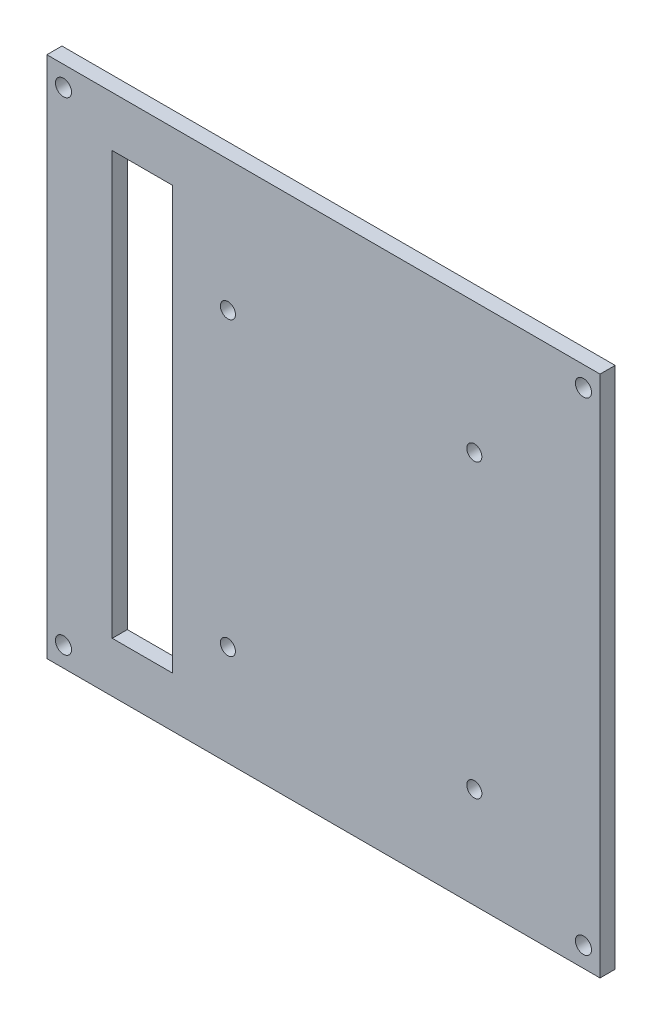
SolidWorks part; units mm, degrees
ref_plane "Alzado" through (0, 0, 0) normal (0, 0, 1) x (1, 0, 0)
ref_plane "Planta" through (0, 0, 0) normal (0, 1, 0) x (1, 0, 0)
ref_plane "Vista lateral" through (0, 0, 0) normal (1, 0, 0) x (0, 0, -1)
sketch "Croquis1" plane through (0, 0, 0) normal (0, 0, 1) x (1, 0, 0)
  line L1 (0, 82) -> (110, 82)
  line L2 (0, 82) -> (0, -10)
  line L3 (0, -10) -> (110, -10)
  line L4 (110, 82) -> (110, -10)
  line L5 (0, 82) -> (110, 82)
  line L9 (0, -10) -> (110, -10)
  dimension "D1" = 110
  dimension "D2" = 92
extrude "Saliente-Extruir1" add sketch "Croquis1" along normal blind 3 contours L1 | L3 | L2 L3 L4 L1 region at (55, 36, 0)
sketch "Croquis7" plane through (0, 82, 0) normal (0, 1, 0) x (1, 0, 0)
  line L1 (0, 0) -> (110, 0)
  line L2 (0, 0) -> (0, -3)
  line L3 (0, -3) -> (110, -3)
  line L4 (110, 0) -> (110, -3)
extrude "Saliente-Extruir2" add sketch "Croquis7" along normal blind 6
sketch "Croquis8" plane through (0, -10, 0) normal (0, -1, 0) x (1, 0, 0)
  line L1 (0, 3) -> (110, 3)
  line L2 (0, 3) -> (0, 0)
  line L3 (0, 0) -> (110, 0)
  line L4 (110, 3) -> (110, 0)
extrude "Saliente-Extruir3" add sketch "Croquis8" along normal blind 6
sketch "Croquis9" plane through (0, 0, 3) normal (0, 0, 1) x (1, 0, 0)
  line L1 (110, 88) -> (110, -16) construction
  line L3 (110, -16) -> (0, -16) construction
  circle A0 centre (97.5, -6) radius 2.5
  dimension "D1" = 5
  dimension "D3" = 10
  dimension "D2" = 12.5
sketch "Croquis11" plane through (0, 0, 3) normal (0, 0, 1) x (1, 0, 0)
  line L0 (0, 84) -> (110, 84) construction
  line L1 (0, 88) -> (0, -16) construction
  line L2 (110, 88) -> (110, -16) construction
  line L3 (3.3, 88) -> (3.3, -16) construction
  line L4 (0, 88) -> (110, 88) construction
  line L5 (110, -16) -> (0, -16) construction
  line L6 (106.7, 88) -> (106.7, -16) construction
  line L7 (0, -12) -> (110, -12) construction
  dimension "D1" = 4
  dimension "D2" = 3.3
  dimension "D3" = 3.3
  dimension "D4" = 4
hole_wizard "Taladro de margen para M31" positions "Croquis3D2" profile "Croquis12" hole size "M3" standard "ISO" end condition through all
sketch3d "Croquis3D2"
  line L0 (0, 84, 3) -> (110, 84, 3) construction
  line L1 (3.3, 88, 3) -> (3.3, -16, 3) construction
  line L2 (0, -12, 3) -> (110, -12, 3) construction
  line L3 (106.7, 88, 3) -> (106.7, -16, 3) construction
  point P0 (3.3, 84, 3)
  point P6 (3.3, -12, 3)
  point P10 (106.7, -12, 3)
  point P14 (106.7, 84, 3)
sketch "Croquis12" plane through (3.3, 84, 3) normal (1, 0, 0) x (0, -1, 0)
  line L0 (0, 0) -> (0, 3)
  line L1 (0, 3) -> (1.6, 3)
  line L2 (1.6, 3) -> (1.6, 0)
  line L5 (1.6, 0) -> (0, 0)
  line L11 (0, -6.35) -> (0, 107.95) construction
  dimension "Diámetro de taladro hasta el siguiente" = 3.2
  dimension "Profundidad de taladro hasta el siguiente" = 3
sketch "Croquis13" plane through (0, 0, 3) normal (0, 0, 1) x (1, 0, 0)
  line L0 (36, 88) -> (36, -16) construction
  line L1 (110, -16) -> (0, -16) construction
  line L2 (85, 88) -> (85, -16) construction
  line L3 (55, 88) -> (55, -16) construction
  line L4 (0, 88) -> (0, -16) construction
  line L5 (110, 88) -> (110, -16) construction
  line L6 (0, 88) -> (110, 88) construction
  line L7 (0, 62) -> (110, 62) construction
  circle A0 centre (36, 62) radius 1.5
  circle A1 centre (85, 62) radius 1.5
  circle A2 centre (36, 4) radius 1.5
  circle A3 centre (85, 4) radius 1.5
  dimension "D4" = 3
  dimension "D1" = 19
  dimension "D2" = 49
  dimension "D3" = 58
  dimension "D5" = 20
extrude "Cortar-Extruir2" cut sketch "Croquis13" against normal up to next
sketch "Croquis14" plane through (0, 0, 3) normal (0, 0, 1) x (1, 0, 0)
  line L0 (0, 88) -> (0, -16) construction
  line L1 (13, 78) -> (25, 78)
  line L2 (13, 78) -> (13, -6)
  line L3 (13, -6) -> (25, -6)
  line L4 (25, 78) -> (25, -6)
  line L5 (0, 88) -> (110, 88) construction
  line L6 (110, -16) -> (0, -16) construction
  dimension "D1" = 12
  dimension "D2" = 13
  dimension "D3" = 10
  dimension "D4" = 10
extrude "Cortar-Extruir3" cut sketch "Croquis14" against normal up to next
